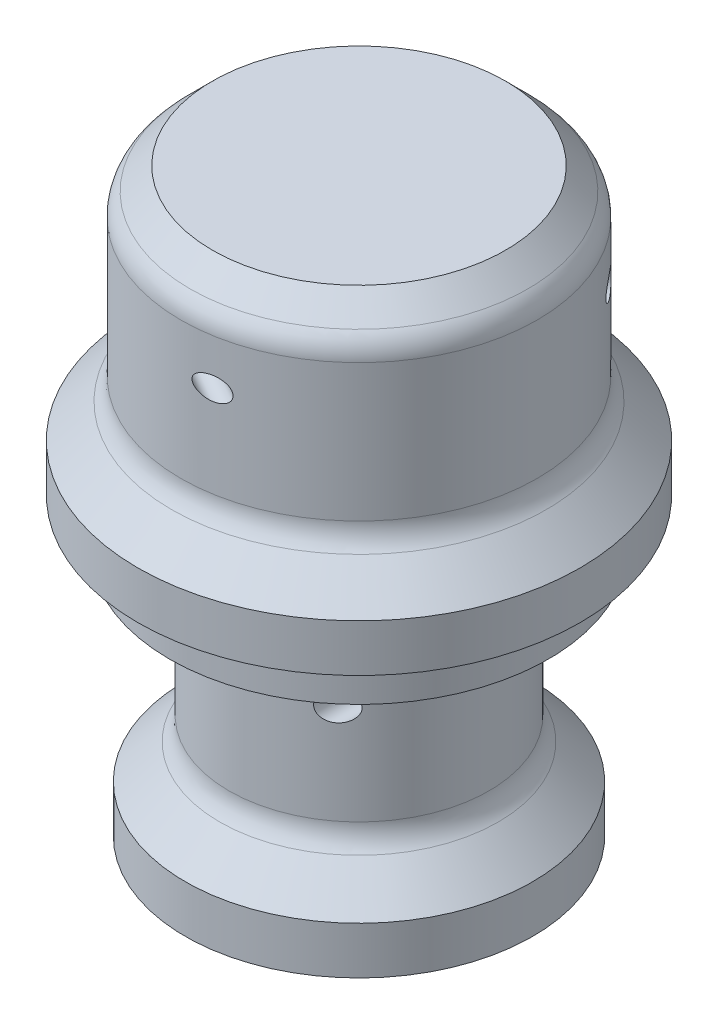
SolidWorks part; units mm, degrees
ref_plane "Plano frontal" through (0, 0, 0) normal (0, 0, 1) x (1, 0, 0)
ref_plane "Plano superior" through (0, 0, 0) normal (0, 1, 0) x (1, 0, 0)
ref_plane "Plano direito" through (0, 0, 0) normal (1, 0, 0) x (0, 0, -1)
sketch "Cut_1" plane through (0, 0, 0) normal (0, 1, 0) x (1, 0, 0)
  line L0 (4.346, 3.5956) -> (4.346, 1.8026) construction
  line L1 (3.987, 2.4982) -> (3.987, 3.99)
  line L2 (4.705, 0) -> (4.705, 3.1111)
  line L3 (3.987, 2.4982) -> (4.346, 2.4982) construction
  line L4 (4.346, 2.4982) -> (4.705, 2.4982) construction
  circle A0 centre (0, 0) radius 4.705
  circle A2 centre (0, 0) radius 5.6406
  circle A4 centre (0, 0) radius 1.087
  dimension "D1" = 9.41
  dimension "D5" = 11.2811
  dimension "D6" = 2.174
  dimension "D2" = 4.346
  dimension "D3" = 0.718
  dimension "D4" = 1.793
sketch "Cut_2" plane through (0, 0, 0) normal (0, 1, 0) x (1, 0, 0)
  line L0 (2.958, 0) -> (2.958, 2.8621)
  line L1 (2.102, 2.0812) -> (2.102, 3.5388)
  line L2 (2.102, 2.0812) -> (2.53, 2.0812) construction
  line L3 (2.53, 2.0812) -> (2.958, 2.0812) construction
  line L4 (2.53, 3.2466) -> (2.53, 1.5326) construction
  circle A0 centre (0, 0) radius 2.958
  circle A1 centre (0, 0) radius 4.116
  circle A2 centre (0, 0) radius 2.392
  circle A3 centre (0, 0) radius 2.847
  dimension "D1" = 5.916
  dimension "D2" = 2.53
  dimension "D5" = 8.232
  dimension "D6" = 4.784
  dimension "D7" = 5.694
  dimension "D3" = 0.856
  dimension "D4" = 1.714
sketch "Esboço4" plane through (0, 0, 0) normal (0, 0, 1) x (1, 0, 0)
  line L0 (0, 0) -> (0, 9.8449) construction
  line L1 (2.958, 0) -> (2.958, 4.36) construction
  line L2 (1.087, 0) -> (1.087, 8.692)
  line L3 (1.087, 8.692) -> (4.705, 12.31)
  line L4 (4.705, 12.31) -> (4.705, 17.384)
  line L5 (4.705, 17.384) -> (0, 17.384)
  line L6 (0, 17.384) -> (0, 19.384)
  line L7 (0, 19.384) -> (5.6406, 19.384)
  line L8 (5.6406, 19.384) -> (5.6406, 10.353)
  line L9 (5.6406, 10.353) -> (4.116, 10.353)
  line L10 (4.116, 10.353) -> (4.116, 1)
  line L11 (4.116, 1) -> (4, 1)
  line L12 (4, 1) -> (4, 0)
  line L13 (4, 0) -> (2.847, 0)
  line L14 (2.392, 1.923) -> (2.392, 3.794)
  line L15 (2.392, 3.794) -> (2.958, 4.36)
  line L16 (2.958, 4.36) -> (2.958, 8.853)
  line L17 (2.958, 8.853) -> (2.587, 8.853)
  line L18 (2.087, 8.353) -> (2.087, 0)
  line L19 (2.087, 0) -> (1.087, 0)
  line L20 (2.392, 0) -> (-2.392, 0) construction
  line L21 (4.116, 1) -> (4.116, 0) construction
  line L22 (2.847, 0) -> (2.847, 0.923)
  line L23 (2.958, 0) -> (-2.958, 0) construction
  line L24 (2.847, 0.923) -> (2.392, 1.923)
  line L25 (4.705, 12.31) -> (4.705, 0) construction
  line L28 (5.6406, 10.353) -> (5.6406, 0) construction
  line L29 (2.392, 1.923) -> (2.392, 0) construction
  line L31 (2.087, 8.353) -> (2.587, 8.853)
  line L32 (2.087, 8.353) -> (2.087, 8.853) construction
  line L33 (2.087, 8.853) -> (2.587, 8.853) construction
  point P17 (0, 0)
  point P26 (2.392, 3.4375)
  point P30 (2.392, 5.3818)
  dimension "D1" = 1
  dimension "D2" = 8
  dimension "D3" = 45
  dimension "D4" = 1
  dimension "D5" = 45
  dimension "D6" = 8.692
  dimension "D7" = 5.059
  dimension "D8" = 2
  dimension "D9" = 1
  dimension "D10" = 8.692
  dimension "D11" = 1.5
  dimension "D12" = 3.794
  dimension "D13" = 0.116
  dimension "D14" = 45
  dimension "D15" = 0.5
  dimension "D16" = 0.923
revolve "Revolução1" add sketch "Esboço4" angle 360 about L0
sketch "Esboço5" plane through (0, 0, 0) normal (0, 0, 1) x (1, 0, 0)
  line L0 (0, 0) -> (0, 16.525) construction
  line L1 (2.392, 0) -> (-2.392, 0) construction
  line L2 (0, 16.525) -> (0, 17.384) construction
  line L3 (0, 16.525) -> (4.346, 16.525) construction
  line L4 (4.346, 16.525) -> (4.346, 0) construction
  line L5 (-4.705, 17.384) -> (4.705, 17.384) construction
  line L6 (-2.087, 0) -> (-2.087, 7.424) construction
  line L7 (4.705, 0) -> (-4.705, 0) construction
  line L8 (-2.087, 7.424) -> (-2.087, 8.853) construction
  line L9 (-2.087, 7.424) -> (-2.53, 7.424) construction
  line L10 (-2.53, 7.424) -> (-2.53, 0) construction
  line L15 (-2.53, 0) -> (0, 0) construction
  line L16 (0, 0) -> (2.53, 0) construction
  line L17 (2.958, 0) -> (-2.958, 0) construction
  circle A0 centre (4.346, 16.525) radius 0.359
  circle A1 centre (-2.53, 7.424) radius 0.429
  dimension "D1" = 0.718
  dimension "D3" = 0.858
  dimension "D2" = 0.859
  dimension "D4" = 1.429
extrude "Inlet_1" cut sketch "Esboço5" against normal through all contours A0
pattern_circular "PadrãoCircular1" count 3 over 360 about axis through (0, 0, 0) along (0, -1, 0) of "Inlet_1" reverse direction yes
extrude "Inlet_2" cut sketch "Esboço5<3>" against normal through all contours A1
sketch "Esboço5<3>" plane through (0, 0, 0) normal (0, 0, 1) x (1, 0, 0) same geometry as "Esboço5"
pattern_circular "PadrãoCircular2" count 2 over 360 about axis through (0, 0, 0) along (0, -1, 0) of "Inlet_2" reverse direction yes
chamfer "Chanfro1" distance 1 angle 45 1 edges at (0, 19.384, -5.6406)
fillet "Filete3" radius 1 1 edges at (0, 18.384, 5.6406)
fillet "Filete_topo" radius 0.5 2 edges at (0, 8.853, -2.958) (0, 17.384, -4.705)
fillet "Filete_base" radius 2 4 edges at (0, 8.692, -1.087) (0, 12.31, -4.705) (0, 1.923, -2.392) (0, 0.923, -2.847)
fillet "Filete5" radius 0.5 2 edges at (0, 4.36, -2.958) (0, 3.794, -2.392)
fillet "Filete4" radius 1 1 edges at (0, 8.353, -2.087)
fillet "Filete6" radius 0.25 1 edges at (0, 8.853, -2.587)
sketch "Esboço6" [suppressed] plane through (0, 0, 0) normal (0, 0, 1) x (1, 0, 0)
  line L0 (5.1406, 10.053) -> (5.1406, 11.3719)
  line L1 (5.1406, 11.3719) -> (5.6406, 11.3719)
  line L2 (5.6406, 11.3719) -> (5.5, 11.5124)
  line L3 (5.5, 11.5124) -> (5.5, 11.0124)
  line L5 (5.6406, 11.0124) -> (5.6406, 10.4124)
  line L6 (5.6406, 10.4124) -> (5.5, 10.553)
  line L7 (5.5, 10.553) -> (5.5, 10.053)
  line L9 (5.5, 10.053) -> (5.1406, 10.053)
  line L10 (5.6406, 11.3719) -> (5.6406, 10.053) construction
  line L16 (5.6406, 11.0124) -> (5.5, 11.0124)
  line L17 (-2.087, 8.853) -> (5.6406, 8.853) construction
  line L18 (5.6406, 10.053) -> (5.6406, 8.853) construction
  line L19 (4.116, 2.984) -> (5.5, 1.6)
  line L20 (5.5, 1.6) -> (5.5, 1)
  line L21 (5.5, 1) -> (5.1406, 1)
  line L22 (5.1406, 1) -> (5.1406, 2.984)
  line L24 (-4.116, 1) -> (4.116, 1) construction
  line L26 (0, 0) -> (0, 8.598) construction
  line L27 (5.5, 10.053) -> (6.4062, 10.053) construction
  line L28 (6.4062, 10.053) -> (6.4062, 10.6124) construction
  line L29 (5.1406, 2.984) -> (4.116, 2.984)
  line L33 (4.116, 2.984) -> (4.116, 1) construction
  circle A0 centre (6.0062, 10.6124) radius 0.4 construction
  point P3 (5.6406, 10.353)
  point P9 (5.5, 11.0124)
  dimension "D9" = 0.8
  dimension "D10" = 0.9062
  dimension "D1" = 0.6
  dimension "D2" = 0.5
  dimension "D3" = 11
  dimension "D4" = 0.5
  dimension "D5" = 45
  dimension "D6" = 1.2
  dimension "D7" = 0.6
  dimension "D8" = 45
revolve "Revolução2" [suppressed] add sketch "Esboço6" angle 360 about L0
sketch "Esboço7" [suppressed] plane through (0, 0, 0) normal (0, 0, 1) x (1, 0, 0)
  line L2 (2.234, 0) -> (10.0389, -6.3203)
  line L3 (0.49, 0) -> (10.0389, -6.3203)
  line L6 (0, 0) -> (0, 1.037) construction
  line L11 (-2.234, 0) -> (-0.49, 0) construction
  line L15 (0, 0) -> (0.0314, 0) construction
  conic Q0 (-2.234, 0) -> (-3.6733, -2.4411) control (-2.234, -0.9447) rho 0.531975
  conic Q1 (-0.49, 0) -> (-3.6733, -2.4411) control (-0.49, -0.3139) rho 0.663527
  dimension "D1" = 51
  dimension "D2" = 56.5
  dimension "D3" = 6.3203
  dimension "D6" = 0.0314
  dimension "D4" = 2.4411
sketch "Esboço8" plane through (0, 0, 0) normal (0, 0, 1) x (1, 0, 0)
  line L0 (-4.116, 8.853) -> (-6, 8.853)
  line L1 (-6, 8.853) -> (-6, 10.353)
  line L2 (-6, 10.353) -> (-7, 10.353)
  line L3 (-7, 10.353) -> (-7, 11.853)
  line L4 (-7, 11.853) -> (-5.6406, 13.2124)
  line L6 (-5.1406, 11.3776) -> (-4.116, 10.353)
  line L7 (-4.116, 10.353) -> (-4.116, 8.853)
  line L8 (-4.116, 1) -> (-5.5, 1)
  line L9 (-5.5, 1) -> (-5.5, 2.5)
  line L10 (-5.5, 2.5) -> (-4.116, 3.884)
  line L11 (-4.116, 3.884) -> (-3.616, 3.884)
  line L12 (-3.616, 3.884) -> (-3.616, 1)
  line L13 (-3.616, 1) -> (-4.116, 1)
  line L14 (-5.6406, 13.2124) -> (-5.1406, 13.2124)
  line L15 (-5.1406, 13.2124) -> (-5.1406, 11.3776)
  line L16 (0, 0) -> (0, 3.5) construction
  line L17 (-1.6728, 9.2778) -> (-4.1192, 11.7242) construction
  line L18 (-5.6406, 13.2124) -> (-5.6406, 10.353) construction
  point P7 (0, 0)
  point P20 (-6.309, 10.353)
  point P21 (0, 0)
  point P24 (-5.6406, 13.2522)
  point P25 (-7.3919, 11.853)
  dimension "D1" = 0.5
  dimension "D2" = 1.5
  dimension "D3" = 45
  dimension "D4" = 11
  dimension "D5" = 1.5
  dimension "D6" = 1.5
  dimension "D7" = 0.5
  dimension "D8" = 12
  dimension "D9" = 45
  dimension "D10" = 14
revolve "Revolução3" add sketch "Esboço8" angle 360 about L16
fillet "Filete7" radius 1 2 edges at (0, 3.884, -4.116) (0, 13.2124, -5.6406)
fillet "Filete8" radius 0.5 1 edges at (0, 8.853, -4.116)
equation "\"D2@Esboço5\"=\"D1@Esboço5\"/2+0.5"
equation "\"D4@Esboço5\"=\"D3@Esboço5\"/2+1.0"
equation "\"D1@Esboço7\"=102/2"
equation "\"D2@Esboço7\"=113/2"
